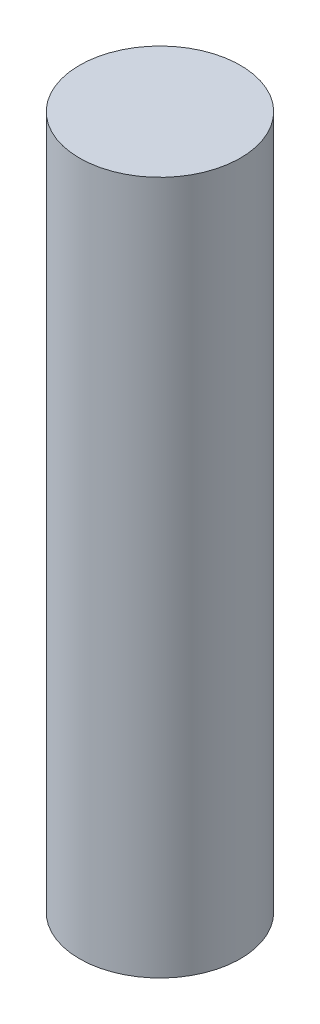
SolidWorks part; units mm, degrees
ref_plane "Front Plane" through (0, 0, 0) normal (0, 0, 1) x (1, 0, 0)
ref_plane "Top Plane" through (0, 0, 0) normal (0, 1, 0) x (1, 0, 0)
ref_plane "Right Plane" through (0, 0, 0) normal (1, 0, 0) x (0, 0, -1)
sketch "Sketch1" plane through (0, 0, 0) normal (0, 1, 0) x (1, 0, 0)
  circle A0 centre (0, 0) radius 5.8
  dimension "D1" = 11.6
extrude "Boss-Extrude1" add sketch "Sketch1" along normal blind 50 contours A0
